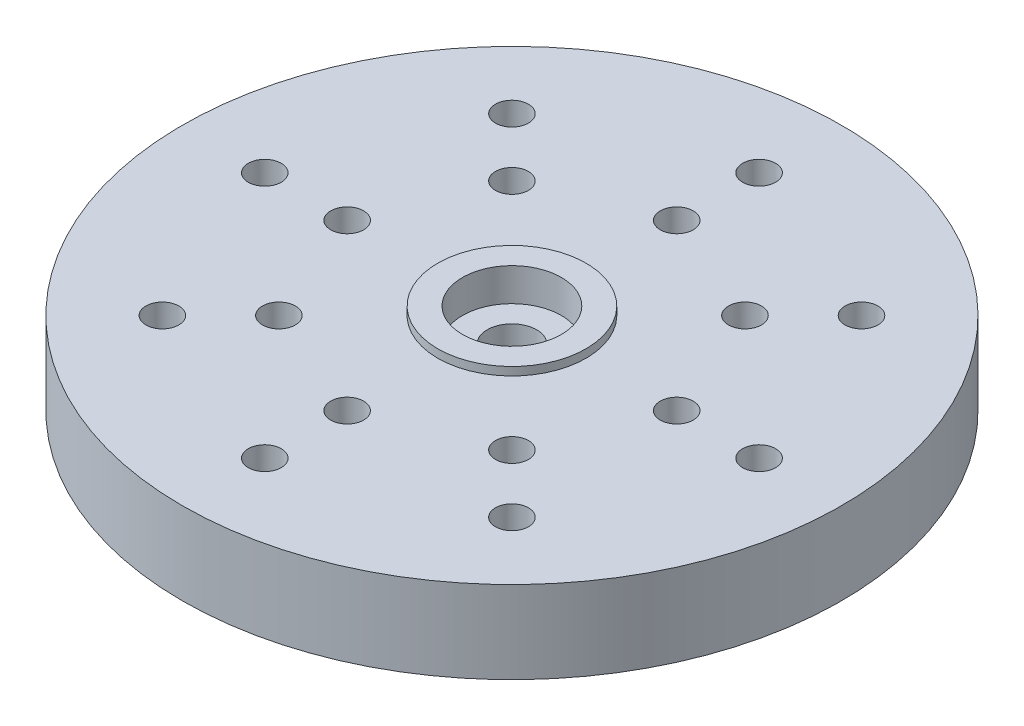
SolidWorks part; units mm, degrees
material "ABS"
ref_plane "Front Plane" through (0, 0, 0) normal (0, 0, 1) x (1, 0, 0)
ref_plane "Top Plane" through (0, 0, 0) normal (0, 1, 0) x (1, 0, 0)
ref_plane "Right Plane" through (0, 0, 0) normal (1, 0, 0) x (0, 0, -1)
sketch "Sketch1" plane through (0, 0, 0) normal (0, 1, 0) x (1, 0, 0)
  circle A0 centre (0, 0) radius 20
  dimension "D1" = 40
extrude "Boss-Extrude1" add sketch "Sketch1" along normal blind 5
sketch "Sketch3" plane through (0, 5, 0) normal (0, 1, 0) x (1, 0, 0)
  circle A0 centre (0, 15) radius 1
  circle A1 centre (0, 10) radius 1
  dimension "D1" = 5
  dimension "D2" = 10
  dimension "D3" = 2
  dimension "D4" = 2
extrude "Cut-Extrude2" cut sketch "Sketch3" against normal blind 10
pattern_circular "CirPattern1" count 8 over 360 about axis through (0, 5, 0) along (0, -1, 0) of "Cut-Extrude2"
sketch "Sketch5" plane through (0, 0, 0) normal (0, -1, 0) x (1, 0, 0)
  circle A0 centre (0, 0) radius 6
  dimension "D1" = 12
extrude "Boss-Extrude3" add sketch "Sketch5" along normal blind 3
sketch "Sketch8" plane through (0, -3, 0) normal (0, -1, 0) x (1, 0, 0)
  line L0 (0, 3.75) -> (0, 3.05) construction
  line L1 (0, 3.05) -> (0.7, 3.6841)
  line L2 (0, 3.05) -> (-0.7, 3.6841)
  line L3 (1.2405, 2.7863) -> (2.1379, 3.0809)
  line L4 (1.2405, 2.7863) -> (0.859, 3.6503)
  line L5 (2.2666, 2.0408) -> (3.2062, 1.9449)
  line L6 (2.2666, 2.0408) -> (2.2694, 2.9853)
  line L7 (2.9007, 0.9425) -> (3.7201, 0.4727)
  line L8 (2.9007, 0.9425) -> (3.2875, 1.8042)
  line L9 (3.0333, -0.3188) -> (3.5907, -1.0813)
  line L10 (3.0333, -0.3188) -> (3.7371, 0.3111)
  line L11 (2.6414, -1.525) -> (2.8405, -2.4483)
  line L12 (2.6414, -1.525) -> (3.5405, -1.2358)
  line L13 (1.7927, -2.4675) -> (1.5991, -3.3919)
  line L14 (1.7927, -2.4675) -> (2.7318, -2.569)
  line L15 (0.6341, -2.9834) -> (0.0813, -3.7491)
  line L16 (0.6341, -2.9834) -> (1.4507, -3.458)
  line L17 (-0.6341, -2.9834) -> (-1.4507, -3.458)
  line L18 (-0.6341, -2.9834) -> (-0.0813, -3.7491)
  line L19 (-1.7927, -2.4675) -> (-2.7318, -2.569)
  line L20 (-1.7927, -2.4675) -> (-1.5991, -3.3919)
  line L21 (-2.6414, -1.525) -> (-3.5405, -1.2358)
  line L22 (-2.6414, -1.525) -> (-2.8405, -2.4483)
  line L23 (-3.0333, -0.3188) -> (-3.7371, 0.3111)
  line L24 (-3.0333, -0.3188) -> (-3.5907, -1.0813)
  line L25 (-2.9007, 0.9425) -> (-3.2875, 1.8042)
  line L26 (-2.9007, 0.9425) -> (-3.7201, 0.4727)
  line L27 (-2.2666, 2.0408) -> (-2.2694, 2.9853)
  line L28 (-2.2666, 2.0408) -> (-3.2062, 1.9449)
  line L29 (-1.2405, 2.7863) -> (-0.859, 3.6503)
  line L30 (-1.2405, 2.7863) -> (-2.1379, 3.0809)
  circle A0 centre (0, 0) radius 3.75 construction
  arc A1 (-0.7, 3.6841) -> (0.7, 3.6841) centre (0, 0) cw construction
  arc A2 (0.7, 3.6841) -> (0.9, 3.6404) centre (0, 0) cw
  arc A3 (2.1379, 3.0809) -> (2.3029, 2.9596) centre (0, 0) cw
  arc A4 (3.2062, 1.9449) -> (3.3076, 1.7671) centre (0, 0) cw
  arc A5 (3.7201, 0.4727) -> (3.7403, 0.269) centre (0, 0) cw
  arc A6 (3.5907, -1.0813) -> (3.5264, -1.2756) centre (0, 0) cw
  arc A7 (2.8405, -2.4483) -> (2.7027, -2.5996) centre (0, 0) cw
  arc A8 (1.5991, -3.3919) -> (1.4117, -3.4742) centre (0, 0) cw
  arc A9 (0.0813, -3.7491) -> (-0.1235, -3.748) centre (0, 0) cw
  arc A10 (-1.4507, -3.458) -> (-1.6372, -3.3737) centre (0, 0) cw
  arc A11 (-2.7318, -2.569) -> (-2.8679, -2.4161) centre (0, 0) cw
  arc A12 (-3.5405, -1.2358) -> (-3.6027, -1.0408) centre (0, 0) cw
  arc A13 (-3.7371, 0.3111) -> (-3.7145, 0.5145) centre (0, 0) cw
  arc A14 (-3.2875, 1.8042) -> (-3.1841, 1.9809) centre (0, 0) cw
  arc A15 (-2.2694, 2.9853) -> (-2.1031, 3.1047) centre (0, 0) cw
  arc A16 (-0.859, 3.6503) -> (-0.6585, 3.6917) centre (0, 0) cw
  point P64 (0, 0)
extrude "Cut-Extrude5" cut sketch "Sketch8" against normal through all contours A16 L29 L30 A15 L27 L28 A14 L25 L26 A13 L23 L24 A12 L21 L22 A11 L19 L20 A10 L17 L18 A9 L15 L16 A8 L13 L14 A7 L11 L12 A6 L9 L10 A5 L7 L8 A4 L5 L6 A3 L3 L4 A2 L1 L2 region at (0, -3, 0)
sketch "Sketch4" plane through (0, 5, 0) normal (0, 1, 0) x (1, 0, 0)
  circle A0 centre (0, 0) radius 4.5
  dimension "D1" = 9
extrude "Boss-Extrude4" add sketch "Sketch4" along normal blind 0.5 and the other way blind 4.96
sketch "Sketch10" plane through (0, 5.5, 0) normal (0, 1, 0) x (1, 0, 0)
  circle A0 centre (0, 0) radius 3
  dimension "D1" = 6
extrude "Cut-Extrude6" cut sketch "Sketch10" against normal blind 2
sketch "Sketch11" plane through (0, 3.5, 0) normal (0, 1, 0) x (1, 0, 0)
  circle A0 centre (0, 0) radius 1.5
  dimension "D1" = 3
extrude "Cut-Extrude7" cut sketch "Sketch11" against normal through all
